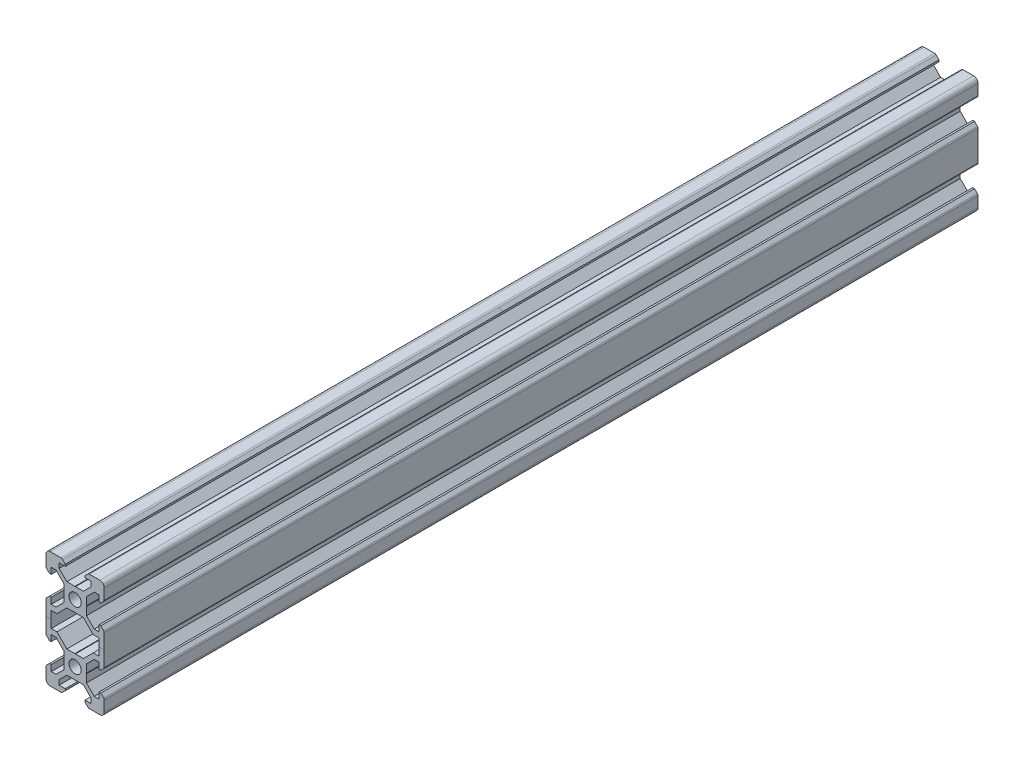
SolidWorks part; units mm, degrees
material "6063-T5"
ref_plane "Front" through (0, 0, 0) normal (0, 0, 1) x (1, 0, 0)
ref_plane "Top" through (0, 0, 0) normal (0, 1, 0) x (1, 0, 0)
ref_plane "Right" through (0, 0, 0) normal (1, 0, 0) x (0, 0, -1)
sketch "Sketch1" plane through (0, 0, 0) normal (0, 0, 1) x (1, 0, 0)
  line L0 (-8.5, 10) -> (-10, 8.5) construction
  line L1 (-8.5, 10) -> (-4.8628, 10)
  line L2 (-10, 8.5) -> (-10, 4.8628)
  line L4 (10, 8.5) -> (10, 4.8628)
  line L5 (-10, 10) -> (10, -10) construction
  line L6 (-10, -10) -> (10, 10) construction
  line L7 (8.2, -5.5) -> (8.2, -3.3865)
  line L8 (-8.2, -5.5) -> (-8.2, -3.3865)
  line L9 (-5.5, 8.2) -> (-3.3865, 8.2)
  line L10 (-8.2, -12.7) -> (-8.2, -7.3)
  line L11 (-3.9005, 2.8395) -> (-6.561, 5.5)
  line L12 (-6.561, 5.5) -> (-8.2, 5.5)
  line L13 (-2.8395, -3.9005) -> (-0.1, -3.9005)
  line L14 (-3.9005, -2.8395) -> (-3.9005, -0.1)
  line L15 (-2.8395, 3.9005) -> (-0.1, 3.9005)
  line L16 (3.9005, -2.8395) -> (3.9005, -0.1)
  line L17 (-8.2, 3.3865) -> (-8.81, 3.3865)
  line L18 (-8.81, 3.3865) -> (-9.7976, 4.3741)
  line L19 (8.5, 10) -> (10, 8.5) construction
  line L20 (-2.8395, 3.9005) -> (-5.5, 6.561)
  line L21 (-5.5, 6.561) -> (-5.5, 8.2)
  line L22 (-3.3865, 8.2) -> (-3.3865, 8.81)
  line L23 (-3.3865, 8.81) -> (-4.3741, 9.7976)
  line L24 (0, 24.069) -> (0, -33.8154) construction
  line L25 (3.3865, 8.81) -> (4.3741, 9.7976)
  line L26 (3.3865, 8.2) -> (3.3865, 8.81)
  line L27 (5.5, 6.561) -> (5.5, 8.2)
  line L28 (2.8395, 3.9005) -> (5.5, 6.561)
  line L29 (3.3865, 8.2) -> (5.5, 8.2)
  line L30 (4.8628, 10) -> (8.5, 10)
  line L31 (-0.1, 3.9005) -> (0, 3.8005)
  line L32 (0.1, 3.9005) -> (0, 3.8005)
  line L33 (0.1, 3.9005) -> (2.8395, 3.9005)
  line L34 (25.9287, 0) -> (-28.3459, 0) construction
  line L35 (-0.1, -3.9005) -> (0, -3.8005)
  line L36 (0.1, -3.9005) -> (0, -3.8005)
  line L37 (0.1, -3.9005) -> (2.8395, -3.9005)
  line L38 (-3.9005, 0.1) -> (-3.8005, 0)
  line L39 (-3.8005, 0) -> (-3.9005, -0.1)
  line L40 (-3.9005, 0.1) -> (-3.9005, 2.8395)
  line L41 (3.9005, 0.1) -> (3.8005, 0)
  line L42 (3.8005, 0) -> (3.9005, -0.1)
  line L43 (3.9005, 0.1) -> (3.9005, 2.8395)
  line L44 (8.81, 3.3865) -> (9.7976, 4.3741)
  line L45 (8.2, 3.3865) -> (8.81, 3.3865)
  line L46 (6.561, 5.5) -> (8.2, 5.5)
  line L47 (3.9005, 2.8395) -> (6.561, 5.5)
  line L48 (2.8395, -3.9005) -> (5.5, -6.561)
  line L49 (3.9005, -2.8395) -> (6.561, -5.5)
  line L50 (-2.8395, -3.9005) -> (-5.5, -6.561)
  line L51 (-3.9005, -2.8395) -> (-6.561, -5.5)
  line L52 (6.561, -5.5) -> (8.2, -5.5)
  line L53 (-6.561, -5.5) -> (-8.2, -5.5)
  line L54 (-8.81, -3.3865) -> (-9.7976, -4.3741)
  line L55 (-8.2, -3.3865) -> (-8.81, -3.3865)
  line L56 (8.81, -3.3865) -> (9.7976, -4.3741)
  line L57 (8.2, -3.3865) -> (8.81, -3.3865)
  line L58 (8.2, 3.3865) -> (8.2, 5.5)
  line L59 (10, -4.8628) -> (10, -15.1372)
  line L60 (-8.2, 3.3865) -> (-8.2, 5.5)
  line L61 (-10, -4.8628) -> (-10, -15.1372)
  line L62 (-28.3459, -10) -> (-10, -10) construction
  line L63 (-3.9005, -20.1) -> (-3.9005, -22.8395)
  line L64 (-3.9005, -20.1) -> (-3.8005, -20)
  line L65 (-3.8005, -20) -> (-3.9005, -19.9)
  line L66 (3.9005, -20.1) -> (3.9005, -22.8395)
  line L67 (3.9005, -20.1) -> (3.8005, -20)
  line L68 (3.8005, -20) -> (3.9005, -19.9)
  line L69 (6.561, -14.5) -> (8.2, -14.5)
  line L70 (3.9005, -17.1605) -> (6.561, -14.5)
  line L71 (3.9005, -17.1605) -> (3.9005, -19.9)
  line L72 (-3.9005, -17.1605) -> (-3.9005, -19.9)
  line L73 (-3.9005, -17.1605) -> (-6.561, -14.5)
  line L74 (-6.561, -14.5) -> (-8.2, -14.5)
  line L75 (-8.2, -16.6135) -> (-8.81, -16.6135)
  line L76 (-8.81, -16.6135) -> (-9.7976, -15.6259)
  line L77 (8.2, -16.6135) -> (8.81, -16.6135)
  line L78 (8.81, -16.6135) -> (9.7976, -15.6259)
  line L79 (-2.8395, -16.0995) -> (-5.5, -13.439)
  line L80 (-2.8395, -16.0995) -> (-0.1, -16.0995)
  line L81 (-0.1, -16.0995) -> (0, -16.1995)
  line L82 (0.1, -16.0995) -> (0, -16.1995)
  line L83 (0.1, -16.0995) -> (2.8395, -16.0995)
  line L84 (2.8395, -16.0995) -> (5.5, -13.439)
  line L85 (-8.2, -16.6135) -> (-8.2, -14.5)
  line L86 (8.2, -16.6135) -> (8.2, -14.5)
  line L87 (2.8395, -23.9005) -> (5.5, -26.561)
  line L88 (-2.8395, -23.9005) -> (-5.5, -26.561)
  line L89 (-0.1, -23.9005) -> (0, -23.8005)
  line L90 (0.1, -23.9005) -> (0, -23.8005)
  line L91 (0.1, -23.9005) -> (2.8395, -23.9005)
  line L92 (-2.8395, -23.9005) -> (-0.1, -23.9005)
  line L93 (-10, -28.5) -> (-10, -24.8628)
  line L94 (10, -28.5) -> (10, -24.8628)
  line L95 (8.81, -23.3865) -> (9.7976, -24.3741)
  line L96 (-8.81, -23.3865) -> (-9.7976, -24.3741)
  line L97 (-8.2, -23.3865) -> (-8.81, -23.3865)
  line L98 (8.2, -23.3865) -> (8.81, -23.3865)
  line L99 (8.2, -23.3865) -> (8.2, -25.5)
  line L100 (-8.2, -23.3865) -> (-8.2, -25.5)
  line L101 (-6.561, -25.5) -> (-8.2, -25.5)
  line L102 (6.561, -25.5) -> (8.2, -25.5)
  line L103 (3.9005, -22.8395) -> (6.561, -25.5)
  line L104 (-3.9005, -22.8395) -> (-6.561, -25.5)
  line L105 (-5.5, -28.2) -> (-3.3865, -28.2)
  line L106 (3.3865, -28.2) -> (5.5, -28.2)
  line L107 (3.3865, -28.2) -> (3.3865, -28.81)
  line L108 (3.3865, -28.81) -> (4.3741, -29.7976)
  line L109 (-3.3865, -28.2) -> (-3.3865, -28.81)
  line L110 (-3.3865, -28.81) -> (-4.3741, -29.7976)
  line L111 (-8.5, -30) -> (-4.8628, -30)
  line L112 (4.8628, -30) -> (8.5, -30)
  line L113 (-5.5, -26.561) -> (-5.5, -28.2)
  line L114 (5.5, -26.561) -> (5.5, -28.2)
  line L115 (-6.239, -7.3) -> (-8.2, -7.3)
  line L116 (-5.5, -6.561) -> (-6.239, -7.3)
  line L117 (6.239, -7.3) -> (8.2, -7.3)
  line L118 (5.5, -6.561) -> (6.239, -7.3)
  line L119 (-6.239, -12.7) -> (-8.2, -12.7)
  line L120 (-5.5, -13.439) -> (-6.239, -12.7)
  line L121 (5.5, -13.439) -> (6.239, -12.7)
  line L122 (6.239, -12.7) -> (8.2, -12.7)
  line L123 (8.2, -12.7) -> (8.2, -7.3)
  line L125 (10, -10) -> (25.9287, -10) construction
  circle A0 centre (0, 0) radius 2.1
  arc A1 (-8.5, 10) -> (-10, 8.5) centre (-8.5, 8.5) ccw
  arc A2 (10, 8.5) -> (8.5, 10) centre (8.5, 8.5) ccw
  arc A3 (-4.3741, 9.7976) -> (-4.8628, 10) centre (-4.8628, 9.3088) ccw
  arc A4 (4.8628, 10) -> (4.3741, 9.7976) centre (4.8628, 9.3088) ccw
  circle A5 centre (0, -20) radius 2.1
  arc A6 (9.7976, 4.3741) -> (10, 4.8628) centre (9.3088, 4.8628) ccw
  arc A7 (-10, 4.8628) -> (-9.7976, 4.3741) centre (-9.3088, 4.8628) ccw
  arc A8 (-10, -4.8628) -> (-9.7976, -4.3741) centre (-9.3088, -4.8628) cw
  arc A9 (9.7976, -4.3741) -> (10, -4.8628) centre (9.3088, -4.8628) cw
  arc A10 (-10, -15.1372) -> (-9.7976, -15.6259) centre (-9.3088, -15.1372) ccw
  arc A11 (9.7976, -15.6259) -> (10, -15.1372) centre (9.3088, -15.1372) ccw
  arc A12 (-10, -24.8628) -> (-9.7976, -24.3741) centre (-9.3088, -24.8628) cw
  arc A13 (9.7976, -24.3741) -> (10, -24.8628) centre (9.3088, -24.8628) cw
  arc A14 (4.8628, -30) -> (4.3741, -29.7976) centre (4.8628, -29.3088) cw
  arc A15 (-4.3741, -29.7976) -> (-4.8628, -30) centre (-4.8628, -29.3088) cw
  arc A16 (-8.5, -30) -> (-10, -28.5) centre (-8.5, -28.5) cw
  arc A17 (10, -28.5) -> (8.5, -30) centre (8.5, -28.5) cw
  point P17 (-9.25, 9.25)
  point P21 (9.25, 9.25)
  dimension "D2" = 4.2
  dimension "D4" = 1.5
  dimension "D3" = 20
  dimension "D5" = 0.529
  dimension "D6" = 6.773
  dimension "D7" = 90
  dimension "D8" = 11
  dimension "D9" = 0.61
  dimension "D10" = 0.1
  dimension "D11" = 0.1
  dimension "D12" = 0.1
  dimension "D13" = 0.1
  dimension "D14" = 5.679
  dimension "D15" = 1.639
  dimension "D16" = 1.8
  dimension "D17" = 90
  dimension "D18" = 6.773
  dimension "D19" = 90
  dimension "D20" = 20
  dimension "D21" = 1.8
extrude "Boss-Extrude2" add sketch "Sketch1" along normal blind 300
sketch "Sketch2" plane through (0, 0, 0) normal (0, 0, -1) x (-1, 0, 0)
  line L0 (-10, -10) -> (10, -10)
  line L1 (-10, -15.1372) -> (-10, -4.8628) construction
  line L2 (10, -4.8628) -> (10, -15.1372) construction
split line "SideFixture1 - SplitLine"
sketch "Sketch3" plane through (0, 0, 300) normal (0, 0, 1) x (1, 0, 0)
  line L0 (-10, -10) -> (10, -10)
  line L1 (-10, -4.8628) -> (-10, -15.1372) construction
  line L2 (10, -15.1372) -> (10, -4.8628) construction
split line "SideFixture2 - SplitLine"
sketch "Sketch4" plane through (0, 10, 0) normal (0, 1, 0) x (1, 0, 0)
  line L0 (-8.5, -150) -> (8.5, -150)
  line L1 (-8.5, -300) -> (-8.5, 0) construction
  line L2 (8.5, -300) -> (8.5, 0) construction
split line "SideFixture3 - SplitLine"
